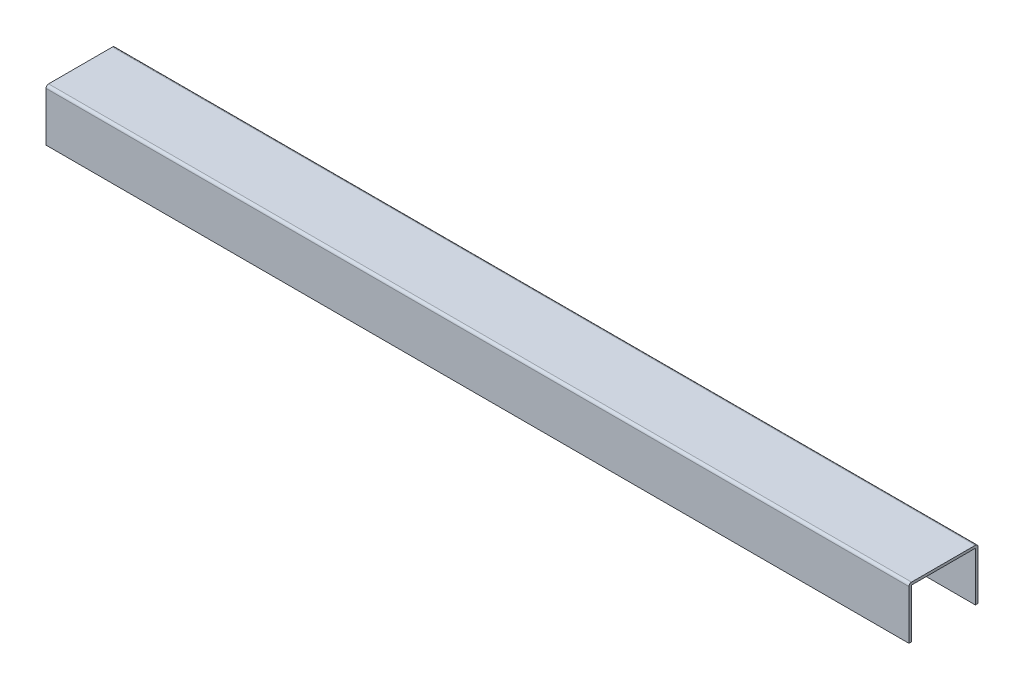
SolidWorks part; units mm, degrees
ref_plane "Спереди" through (0, 0, 0) normal (0, 0, 1) x (1, 0, 0)
ref_plane "Сверху" through (0, 0, 0) normal (0, 1, 0) x (1, 0, 0)
ref_plane "Справа" through (0, 0, 0) normal (1, 0, 0) x (0, 0, -1)
sketch "Эскиз1" plane through (0, 0, 0) normal (1, 0, 0) x (0, 0, -1)
  line L1 (3, 0) -> (77, 0)
  line L2 (0, 3) -> (0, 77)
  line L3 (3, 80) -> (77, 80)
  line L4 (80, 3) -> (80, 77)
  arc A0 (0, 3) -> (3, 0) centre (3, 3) ccw
  arc A1 (77, 0) -> (80, 3) centre (77, 3) ccw
  arc A2 (77, 80) -> (80, 77) centre (77, 77) cw
  arc A3 (0, 77) -> (3, 80) centre (3, 77) cw
  point P7 (0, 0)
  dimension "D1" = 3
extrude "Вытянуть-Тонкостенный1" add sketch "Эскиз1" along normal blind 1000 thin thin type one direction reverse wall 3
sketch "Эскиз2" plane through (0, 0, -80) normal (0, 0, -1) x (-1, 0, 0)
  line L0 (-1000, 3) -> (-1000, 77) construction
  line L1 (-1000, 20) -> (0, 20)
  line L2 (-1000, 20) -> (-1000, 0)
  line L3 (-1000, 0) -> (0, 0)
  line L4 (0, 20) -> (0, 0)
extrude "Вырез-Вытянуть1" cut sketch "Эскиз2" against normal through all
